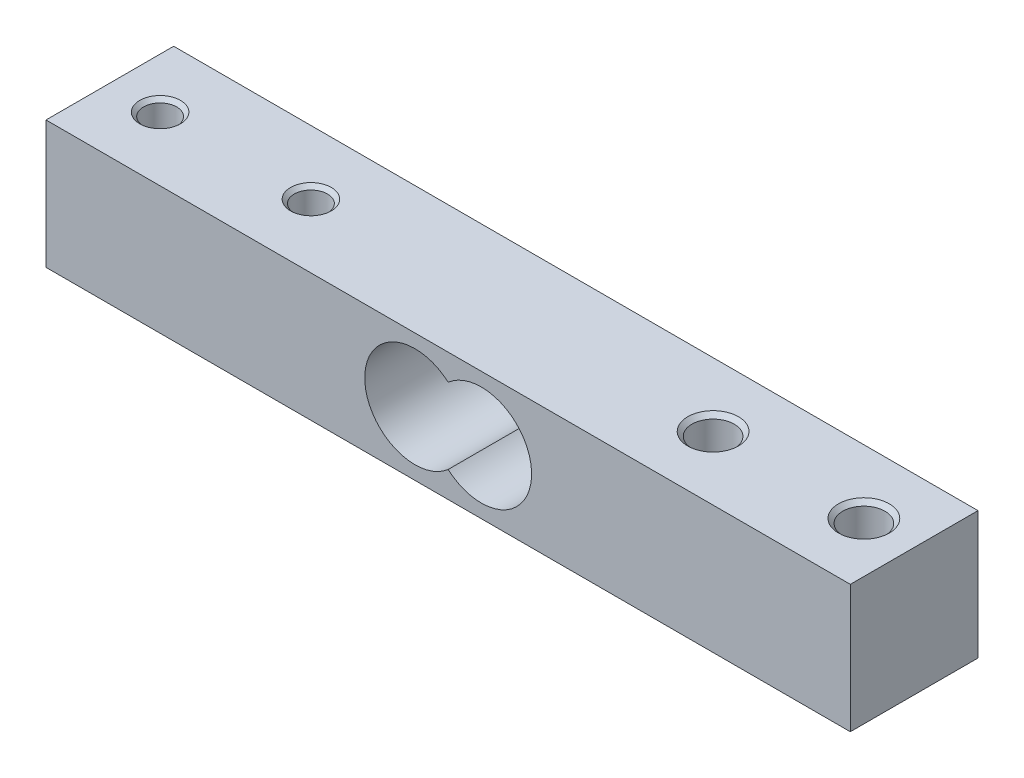
SolidWorks part; units mm, degrees
ref_plane "Front Plane" through (0, 0, 0) normal (0, 0, 1) x (1, 0, 0)
ref_plane "Top Plane" through (0, 0, 0) normal (0, 1, 0) x (1, 0, 0)
ref_plane "Right Plane" through (0, 0, 0) normal (1, 0, 0) x (0, 0, -1)
sketch "Sketch1" plane through (0, 0, 0) normal (0, 1, 0) x (1, 0, 0)
  line L1 (-40, -6.35) -> (40, -6.35)
  line L2 (-40, -6.35) -> (-40, 6.35)
  line L3 (-40, 6.35) -> (40, 6.35)
  line L4 (40, -6.35) -> (40, 6.35)
  line L5 (-40, -6.35) -> (40, 6.35) construction
  line L6 (-40, 6.35) -> (40, -6.35) construction
  point P0 (0, 0)
  dimension "D1" = 80
  dimension "D2" = 12.7
extrude "Boss-Extrude1" add sketch "Sketch1" along normal blind 12.7
sketch "Sketch4" plane through (0, 0, 6.35) normal (0, 0, 1) x (1, 0, 0)
  line L1 (0, 0) -> (0, 12.7) construction
  line L2 (-40, 12.7) -> (40, 12.7) construction
  arc A0 (0, 2.5937) -> (0, 10.1063) centre (3.3, 6.35) ccw
  arc A1 (0, 10.1063) -> (0, 2.5937) centre (-3.3, 6.35) ccw
  point P6 (0, 6.35)
  dimension "D2" = 10
  dimension "D1" = 3.3
extrude "Cut-Extrude1" cut sketch "Sketch4" against normal through all contours A0 A1
sketch "Sketch6" plane through (0, 12.7, 0) normal (0, 1, 0) x (1, 0, 0)
  line L0 (-40, 0) -> (-35, 0) construction
  line L1 (-40, 6.35) -> (-40, -6.35) construction
  line L2 (-124.0403, 0) -> (124.0403, 0) construction
  line L3 (-35, 0) -> (-20, 0) construction
  line L5 (0, -6.985) -> (0, 6.985) construction
  line L6 (35, 0) -> (20, 0) construction
  line L7 (40, 0) -> (35, 0) construction
  point P13 (0, 0)
  dimension "D1" = 5
  dimension "D2" = 20
sketch "Sketch14" plane through (0, 12.7, 0) normal (0, 1, 0) x (1, 0, 0)
  point P0 (-35, 0)
  point P3 (-20, 0)
hole_wizard "M4 Tapped Hole2" positions "Sketch14" profile "Sketch13" tap size "M4" standard "ISO" end condition through all
sketch "Sketch13" plane through (-35, 12.7, 0) normal (1, 0, 0) x (0, 0, 1)
  line L0 (0, 0) -> (0, 12.7)
  line L1 (0, 12.7) -> (1.65, 12.7)
  line L2 (1.65, 12.7) -> (1.65, 0.375)
  line L3 (1.65, 0.375) -> (2.025, 0)
  line L5 (2.025, 0) -> (0, 0)
  line L6 (-1.65, 0.375) -> (-2.025, 0) construction
  line L11 (0, -6.35) -> (0, 107.95) construction
  dimension "Thru Tap Drill Dia." = 3.3
  dimension "Thru Tap Drill Depth" = 12.7
  dimension "Near C'Sink Dia." = 4.05
  dimension "Near C'Sink Angle" = 90
cosmetic thread "Hole Thread5" parameters "D2"=4
cosmetic thread "Hole Thread6" parameters "D2"=4
sketch "Sketch17" plane through (0, 12.7, 0) normal (0, 1, 0) x (1, 0, 0)
  point P0 (35, 0)
  point P3 (20, 0)
hole_wizard "M5 Tapped Hole1" positions "Sketch17" profile "Sketch16" tap size "M5" standard "ISO" end condition through all
sketch "Sketch16" plane through (35, 12.7, 0) normal (1, 0, 0) x (0, 0, 1)
  line L0 (0, 0) -> (0, 12.7)
  line L1 (0, 12.7) -> (2.1, 12.7)
  line L2 (2.1, 12.7) -> (2.1, 0.425)
  line L3 (2.1, 0.425) -> (2.525, 0)
  line L5 (2.525, 0) -> (0, 0)
  line L6 (-2.1, 0.425) -> (-2.525, 0) construction
  line L11 (0, -6.35) -> (0, 16.4902) construction
  point P2 (0, 16.4902)
  dimension "Thru Tap Drill Dia." = 4.2
  dimension "Thru Tap Drill Depth" = 12.7
  dimension "Near C'Sink Dia." = 5.05
  dimension "Near C'Sink Angle" = 90
cosmetic thread "Hole Thread7" parameters "D2"=5
cosmetic thread "Hole Thread8" parameters "D2"=5
equation "\"e\"= 3.3"
equation "\"D1@Sketch4\"=\"e\""
equation "\"d\"=10"
equation "\"D2@Sketch4\"=\"d\""
